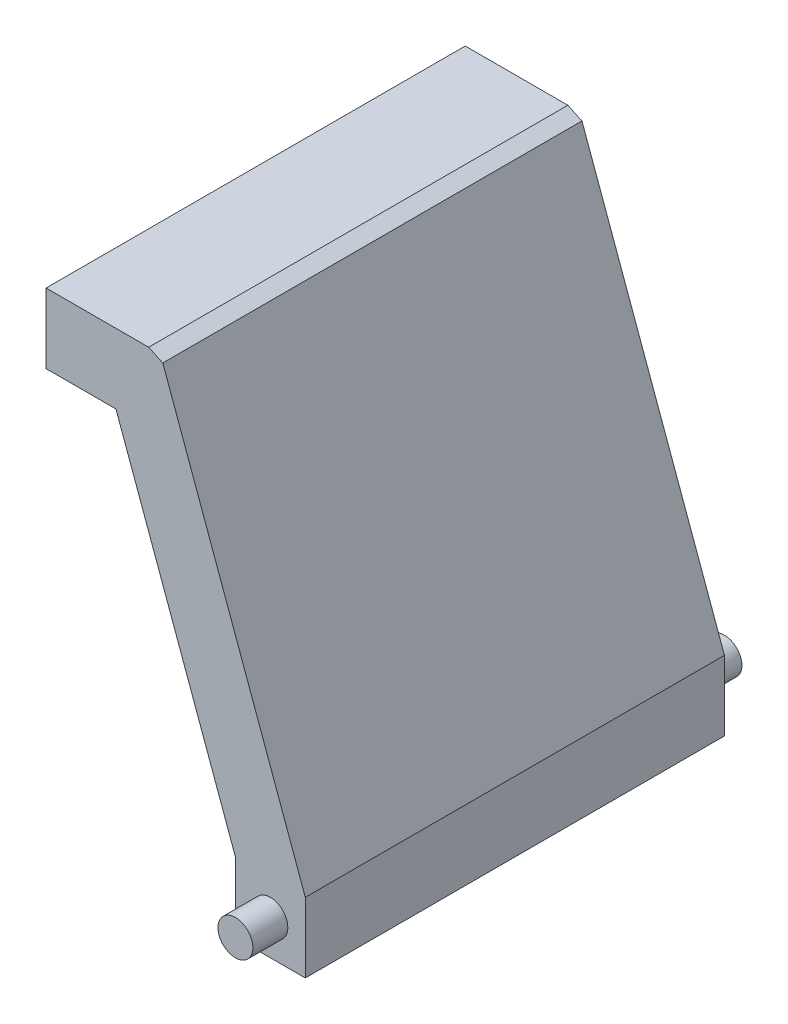
SolidWorks part; units mm, degrees
ref_plane "Front Plane" through (0, 0, 0) normal (0, 0, 1) x (1, 0, 0)
ref_plane "Top Plane" through (0, 0, 0) normal (0, 1, 0) x (1, 0, 0)
ref_plane "Right Plane" through (0, 0, 0) normal (1, 0, 0) x (0, 0, -1)
sketch "Sketch1" plane through (0, 0, 0) normal (0, 0, 1) x (1, 0, 0)
  line L0 (-5, 5) -> (-22.101, 51.9846)
  line L1 (-5, -5) -> (5, -5)
  line L2 (-5, -5) -> (-5, 5)
  line L3 (-5, 5) -> (5, 5)
  line L4 (5, -5) -> (5, 5)
  line L5 (-5, -5) -> (5, 5) construction
  line L6 (-5, 5) -> (5, -5) construction
  line L7 (5, 5) -> (-12.101, 51.9846)
  line L8 (-12.101, 51.9846) -> (-15.7407, 61.9846)
  line L9 (-22.101, 51.9846) -> (-32.101, 51.9846)
  line L10 (-22.101, 51.9846) -> (-22.101, 61.9846)
  line L11 (-22.101, 61.9846) -> (-32.101, 61.9846)
  line L12 (-32.101, 51.9846) -> (-32.101, 61.9846)
  line L13 (-15.7407, 61.9846) -> (-22.101, 61.9846)
  point P0 (0, 0)
  dimension "D1" = 10
  dimension "D2" = 10
  dimension "D3" = 10
  dimension "D4" = 10
extrude "Boss-Extrude1" add sketch "Sketch1" along normal blind 60 contours L12 L9 L10 L11 | L8 L13 L10 L0 L3 L7 | L1 L4 L3 L2 region at (0, 0, 0) region at (-9.9433, 32.6623, 0) region at (-27.101, 56.9846, 0)
chamfer "Chamfer1" distance 3 angle 45 1 edges at (-5, -5, 30)
sketch "Sketch2" plane through (0, 0, 60) normal (0, 0, 1) x (1, 0, 0)
  circle A0 centre (0, 0) radius 2.5
extrude "Boss-Extrude2" add sketch "Sketch2" along normal blind 5 from surface starting at face at (-11.5604, 25.1043, 60)
extrude "Boss-Extrude3" add sketch "Sketch2<2>" against normal blind 5 from surface contours A0 starting at face at (-11.5604, 25.1043, 0)
sketch "Sketch2<2>" plane through (0, 0, 60) normal (0, 0, 1) x (1, 0, 0) same geometry as "Sketch2"
chamfer "Chamfer2" distance 1 angle 45 1 edges at (-15.7407, 61.9846, 30) first distance on face at (-5.3704, 33.4923, 30)
